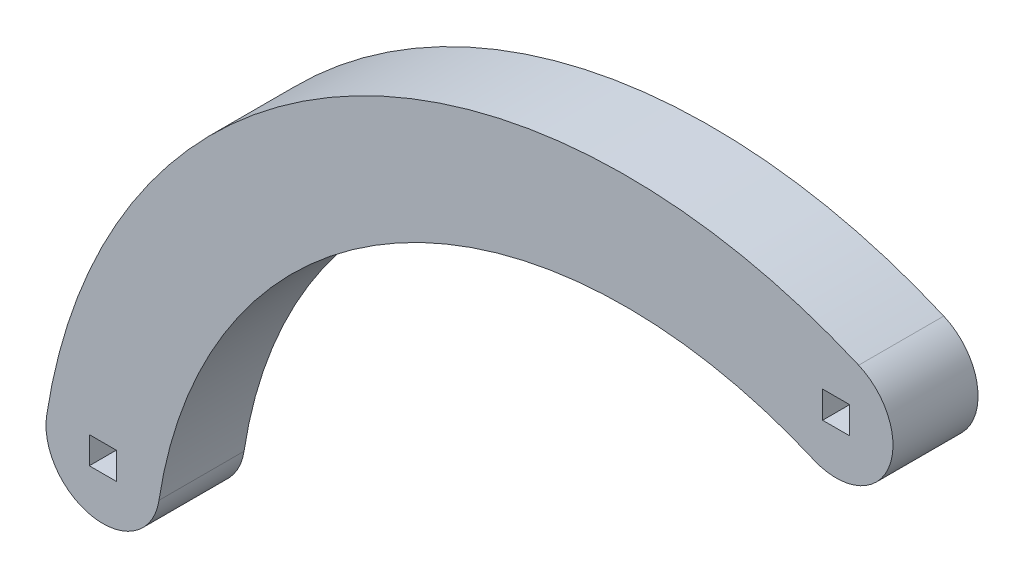
SolidWorks part; units mm, degrees
material "ABS"
ref_plane "Front Plane" through (0, 0, 0) normal (0, 0, 1) x (1, 0, 0)
ref_plane "Top Plane" through (0, 0, 0) normal (0, 1, 0) x (1, 0, 0)
ref_plane "Right Plane" through (0, 0, 0) normal (1, 0, 0) x (0, 0, -1)
sketch "Sketch1" plane through (0, 0, 0) normal (0, 0, 1) x (1, 0, 0)
  line L1 (-1.5875, -1.5875) -> (1.5875, -1.5875)
  line L2 (-1.5875, -1.5875) -> (-1.5875, 1.5875)
  line L3 (-1.5875, 1.5875) -> (1.5875, 1.5875)
  line L4 (1.5875, -1.5875) -> (1.5875, 1.5875)
  line L5 (-1.5875, -1.5875) -> (1.5875, 1.5875) construction
  line L6 (-1.5875, 1.5875) -> (1.5875, -1.5875) construction
  line L7 (84.6057, 46.1432) -> (87.7807, 46.1432)
  line L8 (84.6057, 46.1432) -> (84.6057, 49.3182)
  line L9 (84.6057, 49.3182) -> (87.7807, 49.3182)
  line L10 (87.7807, 46.1432) -> (87.7807, 49.3182)
  line L11 (84.6057, 46.1432) -> (87.7807, 49.3182) construction
  line L12 (84.6057, 49.3182) -> (87.7807, 46.1432) construction
  arc A0 (0, 0) -> (86.1932, 47.7307) centre (61.5293, -9.4208) cw construction
  arc A1 (88.8397, 53.8631) -> (-6.6022, 1.0109) centre (61.5293, -9.4208) ccw
  arc A2 (83.5468, 41.5982) -> (6.6022, -1.0109) centre (61.5293, -9.4208) ccw
  arc A3 (83.5468, 41.5982) -> (88.8397, 53.8631) centre (86.1932, 47.7307) ccw
  arc A4 (-6.6022, 1.0109) -> (6.6022, -1.0109) centre (0, 0) ccw
  point P3 (31.3744, 45.0336)
  point P9 (0, 0)
  point P14 (86.1932, 47.7307)
  dimension "D2" = 3.175
  dimension "D1" = 98.5266
extrude "Boss-Extrude1" add sketch "Sketch1" along normal blind 10
